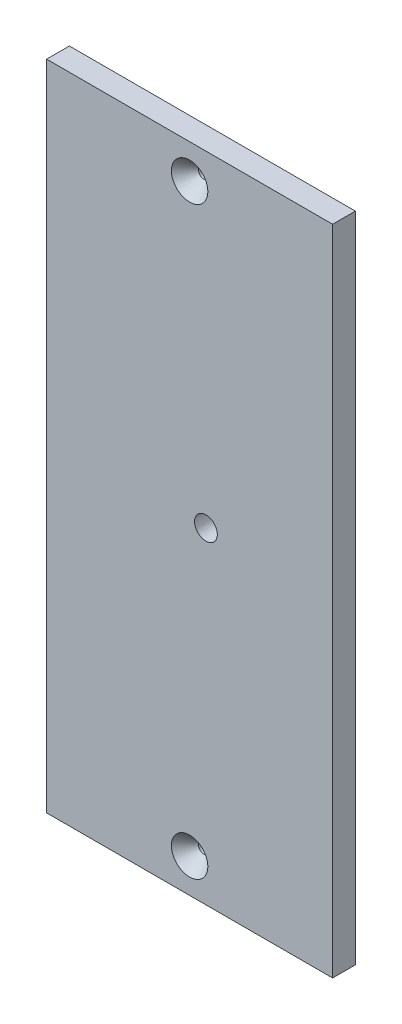
SolidWorks part; units mm, degrees
material "Beech"
ref_plane "Front Plane" through (0, 0, 0) normal (0, 0, 1) x (1, 0, 0)
ref_plane "Top Plane" through (0, 0, 0) normal (0, 1, 0) x (1, 0, 0)
ref_plane "Right Plane" through (0, 0, 0) normal (1, 0, 0) x (0, 0, -1)
sketch "Sketch1" plane through (0, 0, 0) normal (0, 0, 1) x (1, 0, 0)
  line L1 (-234.753, 19.05) -> (-314.5466, 19.05)
  line L2 (-234.753, 19.05) -> (-234.753, -163.1)
  line L3 (-234.753, -163.1) -> (-314.5466, -163.1)
  line L4 (-314.5466, 19.05) -> (-314.5466, -163.1)
  line L5 (-234.753, -163.1) -> (-350.6408, -163.1) construction
  point P5 (0, 0)
  point P8 (-314.5466, -163.1)
  point P10 (0, 0)
  point P11 (-356.9908, -163.1)
  dimension "D1" = 79.7937
extrude "Boss-Extrude1" add sketch "Sketch1" along normal blind 6.35 contours L4 L3 L2 L1
hole_wizard "1/4 (0.25) Diameter Hole1" positions "Sketch4" profile "Sketch5" hole size "1/4" standard "ANSI Inch" end condition through all
sketch "Sketch4" plane through (0, 0, 6.35) normal (0, 0, 1) x (1, 0, 0)
  point P0 (-270.0966, -72.025)
  point P2 (-270.0966, -72.025)
sketch "Sketch5" plane through (-270.0966, -72.025, 6.35) normal (1, 0, 0) x (0, -1, 0)
  line L0 (0, 0) -> (0, 6.35)
  line L1 (0, 6.35) -> (3.175, 6.35)
  line L2 (3.175, 6.35) -> (3.175, 0)
  line L5 (3.175, 0) -> (0, 0)
  line L11 (0, -6.35) -> (0, 107.95) construction
  dimension "Thru Hole Dia." = 6.35
  dimension "Thru Hole Depth" = 6.35
hole_wizard "Hole1" positions "Sketch6" profile "Sketch7" legacy
sketch "Sketch6" plane through (181.0394, -72.025, 6.35) normal (0, 0, 1) x (0, 1, 0)
  line L0 (91.075, 455.6892) -> (-91.075, 455.6892) construction
  point P0 (81.55, 455.6892)
  point P2 (-81.55, 455.6892)
sketch "Sketch7" plane through (-274.6498, 9.525, 6.35) normal (1, 0, 0) x (0, -1, 0)
  line L0 (0, 0) -> (0, 32.7039)
  line L1 (0, 32.7039) -> (1.5875, 31.75)
  line L2 (1.5875, 31.75) -> (1.5875, 4.0177)
  line L3 (1.5875, 4.0177) -> (5.08, 0)
  line L4 (5.08, 0) -> (0, 0)
  line L5 (0, -14.3089) -> (0, 102.4216) construction
  line L6 (0, 32.7039) -> (-1.5875, 31.75) construction
  line L7 (-1.5875, 4.0177) -> (-5.08, 0) construction
  dimension "Diameter" = 3.175
  dimension "Depth" = 31.75
  dimension "C-Sink Diameter" = 10.16
  dimension "C-Sink Angle" = 82
  dimension "Drill Angle" = 118
